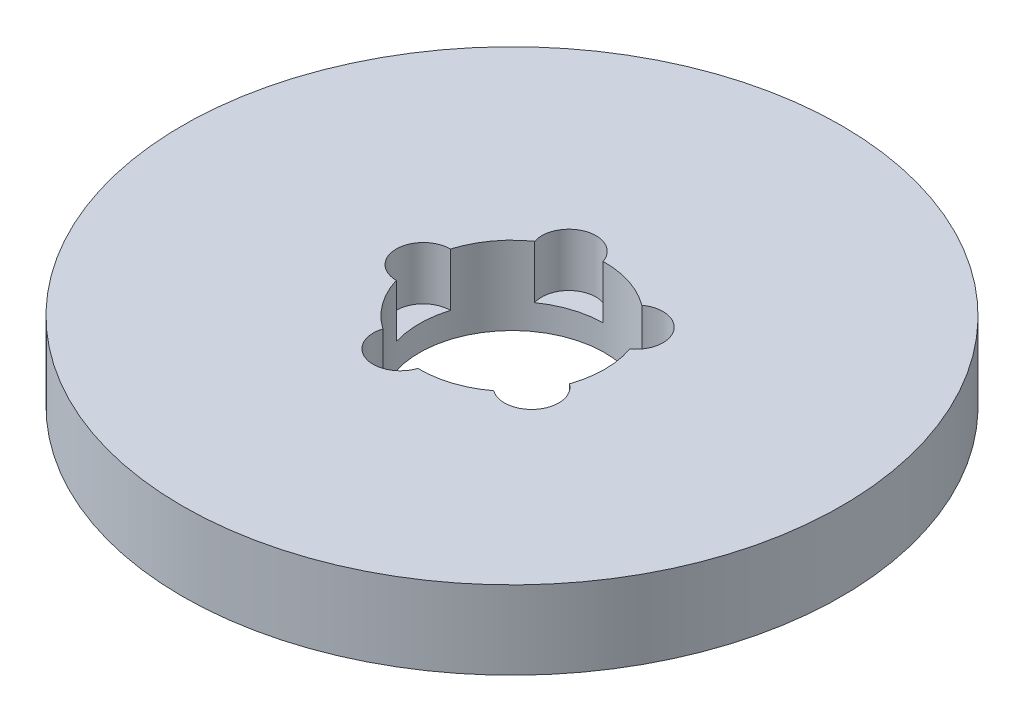
SolidWorks part; units mm, degrees
ref_plane "Front Plane" through (0, 0, 0) normal (0, 0, 1) x (1, 0, 0)
ref_plane "Top Plane" through (0, 0, 0) normal (0, 1, 0) x (1, 0, 0)
ref_plane "Right Plane" through (0, 0, 0) normal (1, 0, 0) x (0, 0, -1)
sketch "Sketch1" plane through (0, 0, 0) normal (0, 1, 0) x (1, 0, 0)
  circle A0 centre (0, 0) radius 80
  dimension "FLANGE_OD" = 160
extrude "Boss-Extrude1" add sketch "Sketch1" along normal blind 19
sketch "Sketch2" plane through (0, 0, 0) normal (0, 1, 0) x (1, 0, 0)
  circle A0 centre (0, 0) radius 22.5
  dimension "BORE_D" = 45
extrude "Cut-Extrude1" cut sketch "Sketch2" along normal through all
sketch "Sketch3" plane through (0, 19, 0) normal (0, 1, 0) x (1, 0, 0)
  circle A0 centre (0, 0) radius 21.5242 construction
  circle A1 centre (-21.5242, 0) radius 6.581
  dimension "BOLT_D" = 13.162
  dimension "BOLT_PCD" = 43.0484
extrude "Cut-Extrude2" cut sketch "Sketch3" against normal blind 12.8993
pattern_circular "CirPattern1" count 5 over 360 about axis through (0, 0, 0) along (0, 1, 0) of "Cut-Extrude2"
